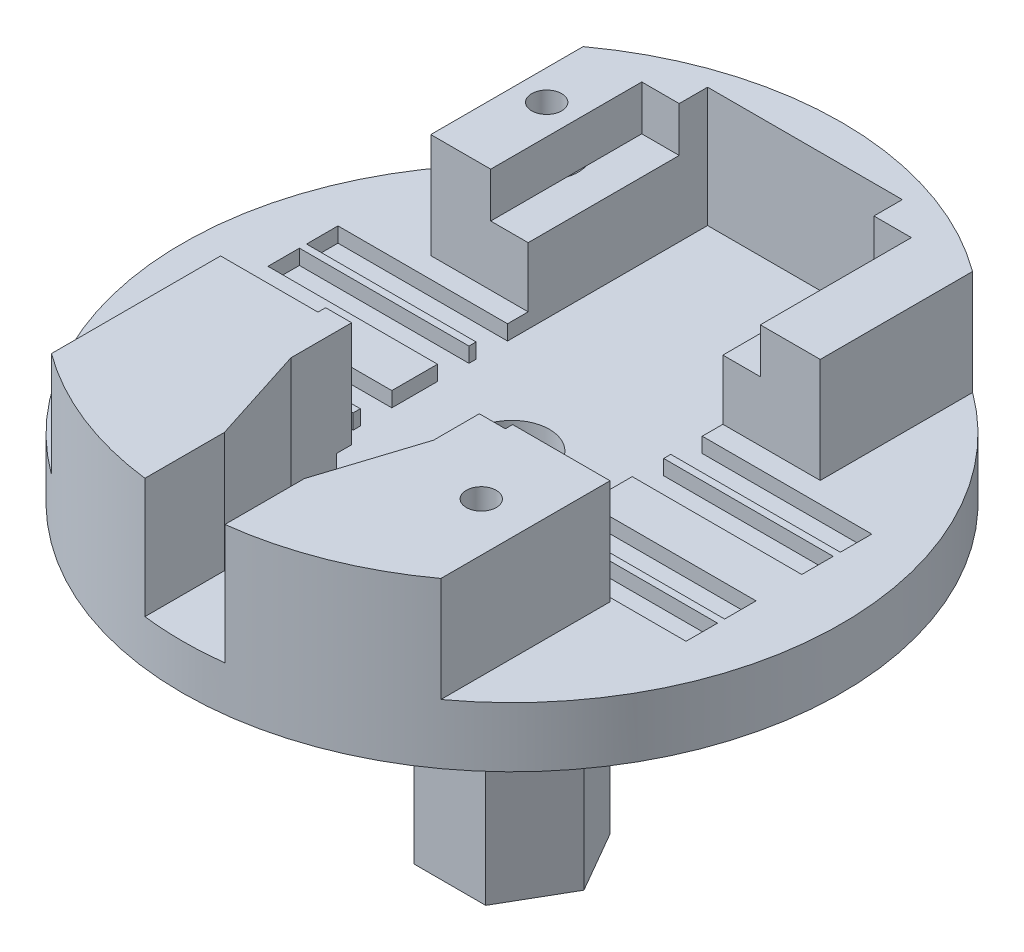
SolidWorks part; units mm, degrees
ref_plane "Front Plane" through (0, 0, 0) normal (0, 0, 1) x (1, 0, 0)
ref_plane "Top Plane" through (0, 0, 0) normal (0, 1, 0) x (1, 0, 0)
ref_plane "Right Plane" through (0, 0, 0) normal (1, 0, 0) x (0, 0, -1)
sketch "Sketch1" plane through (0, 0, 0) normal (0, 1, 0) x (1, 0, 0)
  circle A0 centre (0, 0) radius 22
extrude "Boss-Extrude1" add sketch "Sketch1" along normal blind 9 and the other way blind 2
sketch "Sketch2" plane through (0, 9, 0) normal (0, 1, 0) x (1, 0, 0)
  line L0 (0, 0) -> (0, -22) construction
  circle A0 centre (0, 0) radius 22 construction
ref_plane "Plane4" through (0, -2, 0) normal (0, -1, 0) x (-1, 0, 0)
sketch "Sketch6" plane through (0, -2, 0) normal (0, -1, 0) x (-1, 0, 0)
  circle A0 centre (0, 0) radius 21
  circle A1 centre (0, 0) radius 12.5
extrude "Cut-Extrude5" cut sketch "Sketch6" against normal blind 1
sketch "Sketch7" plane through (0, -2, 0) normal (0, -1, 0) x (-1, 0, 0)
  circle A0 centre (0, 0) radius 8.5
extrude "Boss-Extrude2" add sketch "Sketch7" along normal blind 40 contours A0
sketch "Sketch8" plane through (0, -2, 0) normal (0, -1, 0) x (-1, 0, 0)
  circle A0 centre (0, 0) radius 1.5
extrude "Cut-Extrude6" cut sketch "Sketch8" against normal through all and the other way through all contours A0
sketch "Sketch9" plane through (0, 9, 0) normal (0, 1, 0) x (1, 0, 0)
  line L0 (0, 0) -> (-13.0007, 0) construction
  line L1 (-13.0007, -20.3592) -> (-13.0007, 20.3592)
  line L2 (13, -20.3597) -> (13, 20.3597)
  line L3 (0, 0) -> (13, 0) construction
  arc A0 (13, -20.3597) -> (13, 20.3597) centre (0, 0) ccw
  arc A1 (-13.0007, 20.3592) -> (-13.0007, -20.3592) centre (0, 0) ccw
extrude "Cut-Extrude7" cut sketch "Sketch9" against normal blind 7
ref_plane "Plane5" through (0, -42, 0) normal (0, -1, 0) x (-1, 0, 0)
sketch "Sketch17" plane through (0, -42, 0) normal (0, -1, 0) x (-1, 0, 0)
  circle A0 centre (0, 0) radius 2.4968
extrude "Cut-Extrude14" cut sketch "Sketch17" against normal blind 62
ref_plane "Plane6" through (0, 9, 0) normal (0, 1, 0) x (1, 0, 0)
sketch "Sketch18" plane through (0, 9, 0) normal (0, 1, 0) x (1, 0, 0)
  line L0 (0, -22.0336) -> (0, 23.1421) construction
sketch "Sketch23" plane through (0, 9, 0) normal (0, 1, 0) x (1, 0, 0)
  line L0 (-2.6704, -16.8582) -> (-2.6704, -16.5304)
  line L1 (6.5, 19.5569) -> (6.5, -6.9431)
  line L2 (-6.5, 19.5569) -> (-6.5, -6.9431)
  line L3 (0, -25.25) -> (0, 0) construction
  line L4 (2.6704, -16.8582) -> (2.6704, -16.5304)
  line L5 (4.7624, -10) -> (2.5704, -16.8425) construction
  line L6 (-4.7624, -10) -> (-2.5704, -16.8425) construction
  line L7 (-4.7624, -10) -> (-2.6704, -16.5304)
  line L8 (0, -25.25) -> (-1.0006, -21.9772)
  line L9 (-6.5, 19.5569) -> (6.5, 19.5569)
  line L10 (-6.5, -6.9431) -> (-4.7624, -6.9431)
  line L11 (6.5, -6.9431) -> (4.7624, -6.9431)
  line L12 (-2.6704, -16.8582) -> (-2.6704, -21.9381) construction
  line L13 (2.6704, -16.8582) -> (2.6704, -21.9381) construction
  line L15 (1.0006, -21.9772) -> (0, -25.25)
  line L16 (4.7624, -10) -> (2.6704, -16.5304)
  line L17 (-2.6704, -16.8582) -> (-2.6704, -21.8373)
  line L19 (-4.7624, -10) -> (-4.7624, -6.9431)
  line L21 (4.7624, -10) -> (4.7624, -6.9431)
  line L22 (2.6704, -16.8582) -> (2.6704, -21.8373)
  line L32 (0, -25.592) -> (-1.0756, -22.0738) construction
  line L33 (1.0756, -22.0738) -> (0, -25.592) construction
  line L34 (4.8624, -10.0156) -> (2.6704, -16.8582) construction
  line L35 (4.8624, -10.0156) -> (4.8624, -7.0431) construction
  line L36 (6.6, -7.0431) -> (4.8624, -7.0431) construction
  line L37 (6.6, 19.6569) -> (6.6, -7.0431) construction
  line L38 (-6.6, 19.6569) -> (6.6, 19.6569) construction
  line L39 (-6.6, 19.6569) -> (-6.6, -7.0431) construction
  line L40 (-6.6, -7.0431) -> (-4.8624, -7.0431) construction
  line L41 (-4.8624, -10.0156) -> (-4.8624, -7.0431) construction
  line L42 (-4.8624, -10.0156) -> (-2.6704, -16.8582) construction
  line L43 (2.5704, -16.8425) -> (2.5704, -21.8493) construction
  line L44 (-2.5704, -16.8425) -> (-2.5704, -21.8493) construction
  arc A0 (-2.6704, -21.8373) -> (-1.0006, -21.9772) centre (0, 0) ccw
  arc A1 (1.0006, -21.9772) -> (2.6704, -21.8373) centre (0, 0) ccw
  arc A4 (1.0756, -22.0738) -> (2.6704, -21.9381) centre (0, 0) ccw construction
  arc A5 (-2.6704, -21.9381) -> (-1.0756, -22.0738) centre (0, 0) ccw construction
  arc A6 (-2.5704, -21.8493) -> (-1.0006, -21.9772) centre (0, 0) ccw construction
  arc A7 (1.0006, -21.9772) -> (2.5704, -21.8493) centre (0, 0) ccw construction
  dimension "D1" = 180
ref_plane "Plane10" through (0, 0, 6.4558) normal (0, 0, -1) x (-1, 0, 0)
sketch "Sketch29" plane through (0, 9, 0) normal (0, 1, 0) x (1, 0, 0)
  line L0 (9, 17.6622) -> (9, -6.4558)
  line L1 (9, 17.6622) -> (-9, 17.6622)
  line L2 (9, -6.4558) -> (-9, -6.4558)
  line L3 (0, -6.4558) -> (0, 17.6622) construction
  line L4 (-9, -6.4558) -> (-9, 17.6622)
  point P5 (0, -6.4558)
  point P8 (0, 17.6622)
extrude "Cut-Extrude19" cut sketch "Sketch29" against normal blind 3
sketch "Sketch30" plane through (0, 9, 0) normal (0, 1, 0) x (1, 0, 0)
  line L0 (-8.0021, 17.6622) -> (-8.0021, -6.4558) construction
  line L1 (8.0021, -6.4558) -> (5.5021, -6.4558)
  line L2 (8.0021, -6.4558) -> (8.0021, 7.5442)
  line L3 (8.0021, 7.5442) -> (5.5021, 7.5442)
  line L4 (-8.0021, -6.4558) -> (-8.0021, 7.5442)
  line L5 (5.5021, 7.5442) -> (5.5021, -6.4558)
  line L8 (-5.5021, 7.5442) -> (-5.5021, -6.4558)
  line L9 (-5.5021, 7.5442) -> (-8.0021, 7.5442)
  line L10 (-5.5021, -6.4558) -> (-8.0021, -6.4558)
  point P7 (5.5021, 7.5442)
  dimension "D1" = 2.5
extrude "Cut-Extrude20" cut sketch "Sketch30" against normal blind 6
ref_plane "Plane11" through (0, 3, 0) normal (0, -1, 0) x (-1, 0, 0)
sketch "Sketch32" plane through (0, 3, 0) normal (0, -1, 0) x (-1, 0, 0)
  circle A1 centre (-5.1962, -3) radius 0.85
  circle A3 centre (5.1962, -3) radius 0.85
  circle A5 centre (5.1962, 3) radius 0.85
  circle A6 centre (-5.1962, 3) radius 0.85
  circle A7 centre (0, 6) radius 0.0479
  circle A8 centre (0, 6) radius 0.85
  circle A9 centre (0, -6) radius 0.85
extrude "Cut-Extrude22" [suppressed] cut sketch "Sketch32" against normal blind 11 and the other way through all
ref_plane "Plane12" through (0, 2, 0) normal (0, 1, 0) x (1, 0, 0)
sketch "Sketch33" [suppressed] plane through (0, 2, 0) normal (0, 1, 0) x (1, 0, 0)
  circle A0 centre (5.1962, 3) radius 1.1
  circle A1 centre (5.1962, -3) radius 1.1
  circle A2 centre (-5.1962, 3) radius 1.1
  circle A3 centre (-5.1962, -3) radius 1.1
  circle A4 centre (0, -6) radius 1.1
  circle A5 centre (0, 6) radius 1.1
extrude "Cut-Extrude23" [suppressed] cut sketch "Sketch33" against normal blind 2 and the other way through all
ref_plane "Plane13" through (0, 2, 0) normal (0, 1, 0) x (1, 0, 0)
sketch "Sketch34" plane through (0, 2, 0) normal (0, 1, 0) x (1, 0, 0)
  line L0 (-1.3341, 5.3583) -> (7.9939, 5.3583)
  line L1 (-7.985, 6.6083) -> (-1.2507, 6.6083)
  line L2 (-7.985, 6.6083) -> (-7.985, 5.3583)
  line L3 (-7.985, 5.3583) -> (-1.3341, 5.3583)
  line L4 (7.9939, 6.6083) -> (7.9939, 5.3583)
  line L5 (-1.2507, 6.6083) -> (7.9939, 6.6083)
  line L6 (8.0021, -6.4558) -> (-8.0021, -6.4558)
  line L7 (-8.0021, -6.4558) -> (-8.0021, -5.2058)
  line L8 (-8.0021, 7.5442) -> (-8.0021, -6.4558) construction
  line L9 (-8.0021, -5.2058) -> (8.0021, -5.2058)
  line L10 (8.0021, -5.2058) -> (8.0021, -6.4558)
extrude "Cut-Extrude27" [suppressed] cut sketch "Sketch34" against normal blind 2
ref_plane "Plane14" through (0, -6.5, 0) normal (0, 1, 0) x (1, 0, 0)
sketch "Sketch35" plane through (0, -6.5, 0) normal (0, 1, 0) x (1, 0, 0)
  circle A0 centre (0, 0) radius 8.5
  circle A1 centre (0, 0) radius 9.1
extrude "Boss-Extrude4" add sketch "Sketch35" along normal blind 2 and the other way blind 2
ref_plane "Plane15" through (0, -17, 0) normal (0, 1, 0) x (1, 0, 0)
sketch "Sketch36" plane through (0, -17, 0) normal (0, 1, 0) x (1, 0, 0)
  circle A0 centre (0, 0) radius 8.3
  circle A1 centre (0, 0) radius 8.5
extrude "Cut-Extrude28" cut sketch "Sketch36" against normal blind 1.5 and the other way blind 1.5
ref_plane "Plane16" through (0, -21, 0) normal (0, 1, 0) x (1, 0, 0)
ref_plane "Plane17" through (0, -25, 0) normal (0, 1, 0) x (1, 0, 0)
ref_plane "Plane18" through (0, -29, 0) normal (0, 1, 0) x (1, 0, 0)
ref_plane "Plane19" through (0, -33, 0) normal (0, 1, 0) x (1, 0, 0)
ref_plane "Plane20" through (0, -37, 0) normal (0, 1, 0) x (1, 0, 0)
sketch "Sketch39" plane through (0, -21, 0) normal (0, 1, 0) x (1, 0, 0)
  circle A0 centre (0, 0) radius 8.3
  circle A1 centre (0, 0) radius 8.5
extrude "Cut-Extrude30" cut sketch "Sketch39" against normal blind 1.5 and the other way blind 1.5
sketch "Sketch40" plane through (0, -25, 0) normal (0, 1, 0) x (1, 0, 0)
  circle A0 centre (0, 0) radius 8.3
  circle A1 centre (0, 0) radius 8.5
extrude "Cut-Extrude31" cut sketch "Sketch40" against normal blind 1.5 and the other way blind 1.5
sketch "Sketch41" plane through (0, -29, 0) normal (0, 1, 0) x (1, 0, 0)
  circle A0 centre (0, 0) radius 8.35
  circle A1 centre (0, 0) radius 8.5
extrude "Cut-Extrude32" cut sketch "Sketch41" against normal blind 1.5 and the other way blind 1.5
sketch "Sketch42" plane through (0, -33, 0) normal (0, 1, 0) x (1, 0, 0)
  circle A0 centre (0, 0) radius 8.3
  circle A1 centre (0, 0) radius 8.5
extrude "Cut-Extrude33" cut sketch "Sketch42" against normal blind 1.5 and the other way blind 1.5
sketch "Sketch43" plane through (0, -37, 0) normal (0, 1, 0) x (1, 0, 0)
  circle A0 centre (0, 0) radius 8.3
  circle A1 centre (0, 0) radius 8.5
extrude "Cut-Extrude34" cut sketch "Sketch43" against normal blind 1.5 and the other way blind 1.5
sketch "Sketch44" plane through (0, 0, 0) normal (0, 0, 1) x (1, 0, 0)
  line L0 (0, 0) -> (0, -16.9756) construction
  line L1 (0, -16.9756) -> (0, -29.0422) construction
  circle A0 centre (0, -16.9756) radius 1
  circle A1 centre (0, -29.0422) radius 1
extrude "Cut-Extrude35" cut sketch "Sketch44" against normal through all and the other way through all
ref_axis "Axis1" through (0, -42, 0) along (0, 1, 0)
ref_plane "Plane21" through (0, 0, 0) normal (0.866, 0, 0.5) x (0, 1, 0)
sketch "Sketch45" plane through (0, 0, 0) normal (0.866, 0, 0.5) x (0, 1, 0)
  line L0 (0, 0) -> (-21.1015, 0) construction
  line L1 (-21.1015, 0) -> (-33.0495, 0) construction
  circle A0 centre (-21.1015, 0) radius 1
  circle A1 centre (-33.0495, 0) radius 1
extrude "Cut-Extrude36" cut sketch "Sketch45" against normal through all and the other way through all
ref_plane "Plane22" through (0, 0, 0) normal (0.866, 0, -0.5) x (0, 1, 0)
sketch "Sketch46" plane through (0, 0, 0) normal (0.866, 0, -0.5) x (0, 1, 0)
  line L0 (0, 0) -> (-24.961, 0) construction
  line L1 (-24.961, 0) -> (-37.1304, 0) construction
  circle A0 centre (-24.961, 0) radius 1
  circle A1 centre (-37.1304, 0) radius 1
extrude "Cut-Extrude37" cut sketch "Sketch46" against normal through all and the other way through all
ref_plane "Plane23" through (0, 9, 0) normal (0, 1, 0) x (1, 0, 0)
sketch "Sketch47" plane through (0, 9, 0) normal (0, 1, 0) x (1, 0, 0)
  line L1 (13.8544, -6.4558) -> (-13.8777, -6.4558)
  line L2 (13.8544, -6.4558) -> (13.8544, 7.5778)
  line L3 (13.8544, 7.5778) -> (-13.8777, 7.5778)
  line L4 (-13.8777, -6.4558) -> (-13.8777, 7.5778)
extrude "Cut-Extrude38" cut sketch "Sketch47" against normal blind 7
extrude "Cut-Extrude39" cut sketch "Sketch23" against normal blind 8
sketch "Sketch48" plane through (0, 9, 0) normal (0, 1, 0) x (1, 0, 0)
  line L0 (0, 0) -> (0, 34.87) construction
  line L1 (11, 7.5778) -> (11, 19.0526) construction
  line L2 (13, 7.5778) -> (9, 7.5778) construction
  line L3 (11, 19.0526) -> (11, 13.3152) construction
  line L4 (11, 13.3152) -> (0, 0) construction
  line L5 (0, 0) -> (-17.1456, -20.7543) construction
  line L6 (-9.7504, -6.4558) -> (-9.7504, -16.5924) construction
  line L7 (-13.0007, -6.4558) -> (-6.5, -6.4558) construction
  arc A0 (13, 17.7482) -> (-13.0007, 17.7477) centre (0, 0) ccw construction
  circle A3 centre (-11, 13.3152) radius 1
  circle A4 centre (9.7504, -11.8025) radius 1
  dimension "D1" = 39.561
extrude "Cut-Extrude40" cut sketch "Sketch48" against normal blind 9
sketch "Sketch49" plane through (0, -1, 0) normal (0, -1, 0) x (1, 0, 0)
  circle A2 centre (-11, -13.3152) radius 2.1
  circle A3 centre (9.7504, 11.8025) radius 2.1
sketch "Sketch50" plane through (0, -42, 0) normal (0, -1, 0) x (1, 0, 0)
  line L0 (4.9897, 0.0006) -> (-4.9897, -0.0006) construction
  line L2 (-4.9897, -0.0006) -> (-2.4943, -4.3215)
  line L3 (-2.4943, -4.3215) -> (2.4953, -4.3209)
  line L4 (2.4953, -4.3209) -> (4.9897, 0.0006)
  line L5 (4.9897, 0.0006) -> (2.4943, 4.3215)
  line L6 (2.4943, 4.3215) -> (-2.4953, 4.3209)
  line L7 (-2.4953, 4.3209) -> (-4.9897, -0.0006)
  circle A0 centre (0, 0) radius 4.3212 construction
  circle A1 centre (0, 0) radius 6.3883
extrude "Boss-Extrude5" add sketch "Sketch50" against normal blind 2
sketch "Sketch51" plane through (0, 2, 0) normal (0, 1, 0) x (1, 0, 0)
  line L1 (-4.46, 2.575) -> (4.46, 2.575) construction
  line L3 (-17.8187, 4.1) -> (17.8187, 4.1)
  line L4 (-17.8187, 4.1) -> (-17.8187, 6.2)
  line L5 (-17.8187, 6.2) -> (17.8187, 6.2)
  line L6 (17.8187, 4.1) -> (17.8187, 6.2)
  line L7 (-17.8187, 4.1) -> (17.8187, 6.2) construction
  line L8 (-17.8187, 6.2) -> (17.8187, 4.1) construction
  line L9 (-4.46, -2.575) -> (4.46, -2.575) construction
  line L10 (-17.8187, 3.625) -> (17.8187, 3.625)
  line L11 (-17.8187, 3.625) -> (-17.8187, 1.525)
  line L12 (-17.8187, 1.525) -> (17.8187, 1.525)
  line L13 (17.8187, 3.625) -> (17.8187, 1.525)
  line L14 (-17.8187, 3.625) -> (17.8187, 1.525) construction
  line L15 (-17.8187, 1.525) -> (17.8187, 3.625) construction
  line L17 (-17.8187, -3.625) -> (17.8187, -3.625)
  line L18 (-17.8187, -3.625) -> (-17.8187, -1.525)
  line L19 (-17.8187, -1.525) -> (17.8187, -1.525)
  line L20 (17.8187, -3.625) -> (17.8187, -1.525)
  line L21 (-17.8187, -3.625) -> (17.8187, -1.525) construction
  line L22 (-17.8187, -1.525) -> (17.8187, -3.625) construction
  line L23 (-17.8187, -6.2) -> (17.8187, -6.2)
  line L24 (-17.8187, -6.2) -> (-17.8187, -4.1)
  line L25 (-17.8187, -4.1) -> (17.8187, -4.1)
  line L26 (17.8187, -6.2) -> (17.8187, -4.1)
  line L27 (-17.8187, -6.2) -> (17.8187, -4.1) construction
  line L28 (-17.8187, -4.1) -> (17.8187, -6.2) construction
  point P0 (0, 5.15)
  point P7 (0, 2.575)
  point P14 (0, -2.575)
  point P22 (0, -5.15)
extrude "Cut-Extrude42" cut sketch "Sketch49" against normal blind 7
extrude "Cut-Extrude43" cut sketch "Sketch51" against normal blind 1
sketch "Sketch53" plane through (0, -42, 0) normal (0, -1, 0) x (1, 0, 0)
  circle A0 centre (0, 0) radius 9.1
extrude "Cut-Extrude45" cut sketch "Sketch53" against normal blind 40
sketch "Sketch55" plane through (0, 0, 6.9431) normal (0, 0, -1) x (-1, 0, 0)
  line L0 (-4.7624, 8) -> (-6.1673, 8)
  line L1 (-6.1673, 8) -> (-6.1673, 6)
  line L2 (-6.1673, 6) -> (-6.5, 6)
  line L3 (-6.5, 6) -> (-6.5, 1.9457)
  line L4 (-6.5, 1.9457) -> (-4.7624, 1.9457)
  line L5 (-4.7624, 1.9457) -> (-4.7624, 8)
  line L6 (6.5, 9) -> (4.7624, 9)
  line L7 (4.7624, 9) -> (4.7624, 1.9457)
  line L8 (4.7624, 1) -> (4.7624, 9) construction
  line L9 (4.7624, 1.9457) -> (6.5, 1.9457)
  line L10 (6.5, 1) -> (6.5, 9) construction
  line L11 (6.5, 1.9457) -> (6.5, 9)
extrude "Boss-Extrude6" add sketch "Sketch55" along normal blind 1
sketch "Sketch56" plane through (0, -2, 0) normal (0, -1, 0) x (1, 0, 0)
  line L1 (2.3995, 4.1572) -> (-2.4005, 4.1566)
  line L2 (-2.4005, 4.1566) -> (-4.8, -0.0006)
  line L3 (-4.8, -0.0006) -> (-2.3995, -4.1572)
  line L4 (-2.3995, -4.1572) -> (2.4005, -4.1566)
  line L5 (2.4005, -4.1566) -> (4.8, 0.0006)
  line L6 (4.8, 0.0006) -> (2.3995, 4.1572)
  circle A0 centre (0, 0) radius 4.1569 construction
extrude "Boss-Extrude9" add sketch "Sketch56" along normal blind 20 and the other way blind 2 separate body
